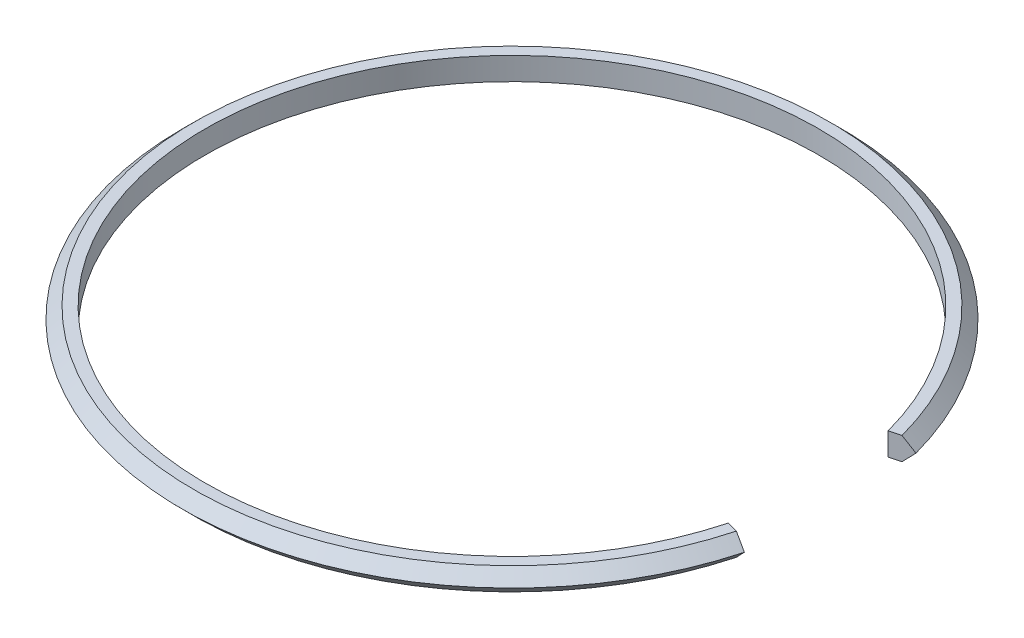
SolidWorks part; units mm, degrees
ref_plane "Plan de face" through (0, 0, 0) normal (0, 0, 1) x (1, 0, 0)
ref_plane "Plan de dessus" through (0, 0, 0) normal (0, 1, 0) x (1, 0, 0)
ref_plane "Plan de droite" through (0, 0, 0) normal (1, 0, 0) x (0, 0, -1)
sketch "Sketch3" plane through (0, 0, 0) normal (0, 1, 0) x (1, 0, 0)
  circle A0 centre (0, 0) radius 13.5
  circle A1 centre (0, 0) radius 14.5
  dimension "D1" = 27
  dimension "D2" = 29
extrude "Boss-Extrude2" add sketch "Sketch3" along normal blind 1
chamfer "Chamfer1" distance 0.5 angle 45 2 edges at (0, 0, 14.5) (0, 1, 14.5)
sketch "Sketch4" plane through (0, 1, 0) normal (0, 1, 0) x (1, 0, 0)
  line L0 (0, 0) -> (14, 0) construction
  line L1 (14, 0) -> (14, 3.7749) construction
  line L2 (13.0345, 3.5146) -> (14, 3.7749)
  line L4 (13.0345, -3.5146) -> (14, -3.7749)
  line L5 (14, 0) -> (14, -3.7749) construction
  circle A0 centre (0, 0) radius 14.5 construction
  arc A2 (14, -3.7749) -> (14, 3.7749) centre (0, 0) ccw
  arc A3 (13.0345, -3.5146) -> (13.0345, 3.5146) centre (0, 0) ccw
  dimension "D2" = 13.5
  dimension "D3" = 1
  dimension "D1" = 14
  dimension "D4" = 1
extrude "Cut-Extrude1" cut sketch "Sketch4" against normal blind 1 contours L2 A2 L4 A3
